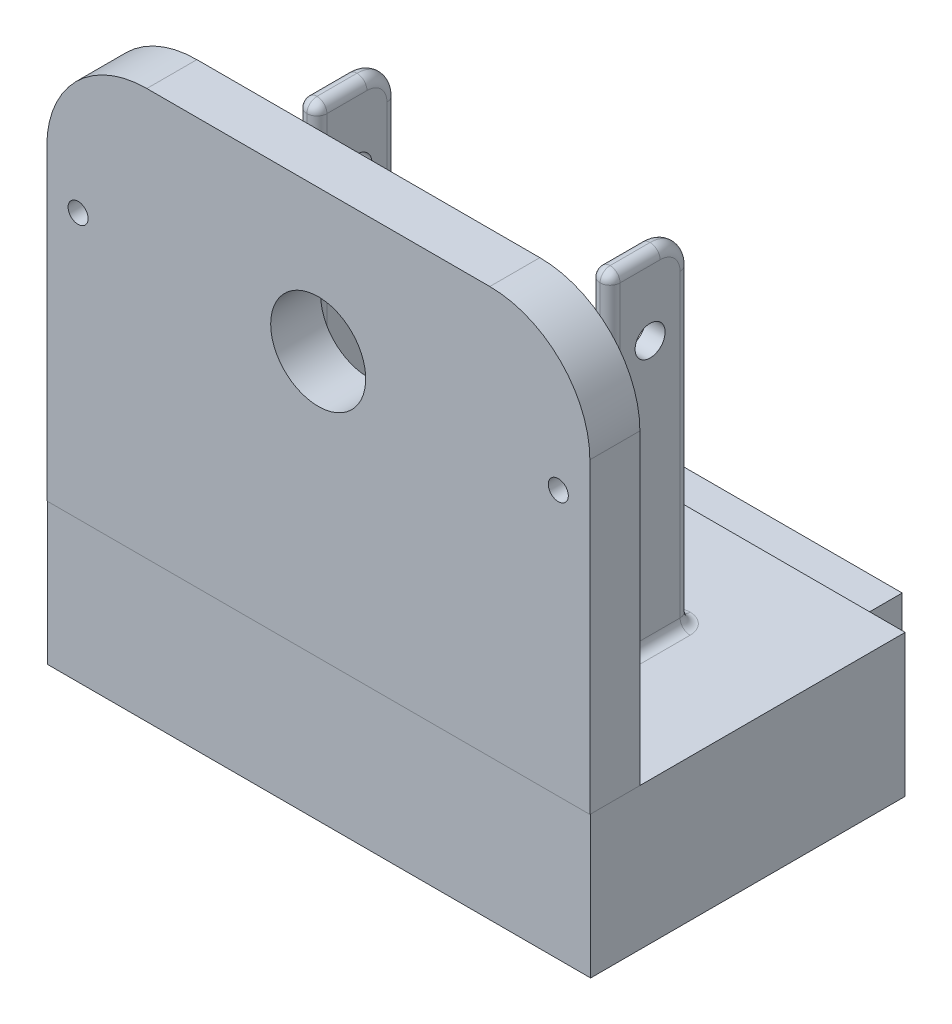
SolidWorks part; units mm, degrees
ref_plane "Front Plane" through (0, 0, 0) normal (0, 0, 1) x (1, 0, 0)
ref_plane "Top Plane" through (0, 0, 0) normal (0, 1, 0) x (1, 0, 0)
ref_plane "Right Plane" through (0, 0, 0) normal (1, 0, 0) x (0, 0, -1)
sketch "Sketch1" plane through (0, 0, 0) normal (0, 1, 0) x (1, 0, 0)
  line L1 (27.15, 8.545) -> (-27.15, 8.545)
  line L2 (27.15, 8.545) -> (27.15, -22.897)
  line L3 (27.15, -22.897) -> (-27.15, -22.897)
  line L4 (-27.15, 8.545) -> (-27.15, -22.897)
  point P0 (0, 0)
  point P5 (-22.15, -8.5023)
  point P6 (0, 0)
  dimension "D1" = 54.3
extrude "Boss-Extrude1" add sketch "Sketch1" along normal blind 11 and the other way blind 3.2
sketch "Sketch2" plane through (0, 0, -8.545) normal (0, 0, -1) x (-1, 0, 0)
  line L0 (-27.15, -3.2) -> (27.15, -3.2) construction
  line L1 (-17.15, 4.5571) -> (17.15, 4.5571)
  line L2 (-17.15, 4.5571) -> (-17.15, 1.044)
  line L3 (-17.15, 1.044) -> (17.15, 1.044)
  line L4 (17.15, 4.5571) -> (17.15, 1.044)
  line L5 (-27.15, 11) -> (-27.15, -3.2) construction
  line L6 (27.15, 11) -> (27.15, -3.2) construction
  line L7 (0, 4.5571) -> (0, 11)
  line L8 (-27.15, 11) -> (27.15, 11) construction
  point P0 (0, 8)
  point P7 (0, -3.2)
  point P18 (-45.1589, 41.0132)
  dimension "D1" = 10
  dimension "D2" = 10
extrude "Boss-Extrude2" add sketch "Sketch2" along normal blind 9.7 contours L4 L1 L2 L3 region at (0, 2.8005, -8.545)
sketch "Sketch3" plane through (0, 11, 0) normal (0, 1, 0) x (1, 0, 0)
  line L1 (27.1542, -17.9782) -> (-27.1273, -17.9782)
  line L2 (27.1542, -17.9782) -> (27.1542, -22.9782)
  line L3 (27.1542, -22.9782) -> (-27.1273, -22.9782)
  line L4 (-27.1273, -17.9782) -> (-27.1273, -22.9782)
extrude "Boss-Extrude3" add sketch "Sketch3" along normal blind 40.7
sketch "Sketch4" plane through (0, 0, 22.897) normal (0, 0, 1) x (1, 0, 0)
  line L0 (0, -3.2) -> (0, 37.5)
  line L1 (-27.15, -3.2) -> (27.15, -3.2) construction
  line L7 (0, 37.5) -> (0, 25.3)
  circle A0 centre (0, 37.5) radius 4.75
  circle A5 centre (-24, 37.5) radius 1
  circle A6 centre (24, 37.5) radius 1
  point P7 (0, 0)
  dimension "D1" = 24
fillet "Fillet1" radius 10 2 edges at (-27.1273, 51.7, 20.4782) (27.1542, 51.7, 20.4782)
sketch "Sketch5" plane through (0, 0, 0) normal (0, 1, 0) x (1, 0, 0)
  line L0 (27.15, -17.9782) -> (27.15, 8.545) construction
  line L1 (13.65, -1.455) -> (15.65, -1.455)
  line L2 (13.65, -1.455) -> (13.65, -9.455)
  line L3 (13.65, -9.455) -> (15.65, -9.455)
  line L4 (15.65, -1.455) -> (15.65, -9.455)
  line L5 (17.15, 8.545) -> (-17.15, 8.545) construction
  line L7 (-27.15, 8.545) -> (-27.15, -22.897) construction
  line L8 (-13.65, -1.455) -> (-15.65, -1.455)
  line L9 (-13.65, -1.455) -> (-13.65, -9.455)
  line L10 (-13.65, -9.455) -> (-15.65, -9.455)
  line L11 (-15.65, -1.455) -> (-15.65, -9.455)
  line L12 (27.15, 8.545) -> (-27.15, 8.545) construction
  point P14 (-14.65, -9.455)
  dimension "D1" = 2
  dimension "D2" = 10
  dimension "D3" = 11.5
  dimension "D4" = 11.5
  dimension "D5" = 8
  dimension "D6" = 10
  dimension "D7" = 2
extrude "Boss-Extrude4" add sketch "Sketch5" along normal blind 45
extrude "Cut-Extrude2" cut sketch "Sketch4" against normal blind 46 and the other way blind 21 contours A6 | A5 | A0
sketch "Sketch8" plane through (15.65, 0, 0) normal (1, 0, 0) x (0, 0, -1)
  line L1 (-9.455, 45) -> (-1.455, 45) construction
  circle A0 centre (-5.455, 37.5) radius 1.5
  point P6 (-5.455, 45)
  dimension "D1" = 7.5
extrude "Cut-Extrude3" cut sketch "Sketch8" against normal blind 46
fillet "Fillet3" radius 3 2 edges at (-14.65, 45, 1.455) (14.65, 45, 1.455)
fillet "Fillet4" radius 1 12 edges at (-15.65, 45, 6.955) (-15.65, 44.1213, 2.3337) (-13.65, 45, 6.955) (-13.65, 44.1213, 2.3337) (13.65, 45, 6.955) (13.65, 44.1213, 2.3337) (15.65, 45, 6.955) (15.65, 44.1213, 2.3337) (-15.65, 26.5, 1.455) (-13.65, 26.5, 1.455) (13.65, 26.5, 1.455) (15.65, 26.5, 1.455)
fillet "Fillet5" radius 1 16 edges at (-13.9429, 11, 1.7479) (-15.3571, 11, 1.7479) (15.3571, 11, 1.7479) (13.9429, 11, 1.7479) (-13.65, 11, 5.955) (-15.65, 11, 5.955) (15.65, 11, 5.955) (13.65, 11, 5.955) (-13.65, 27.5, 9.455) (-15.65, 27.5, 9.455) (-15.3571, 44.7071, 9.455) (-13.9429, 44.7071, 9.455) (15.65, 27.5, 9.455) (13.65, 27.5, 9.455) (13.9429, 44.7071, 9.455) (15.3571, 44.7071, 9.455)
